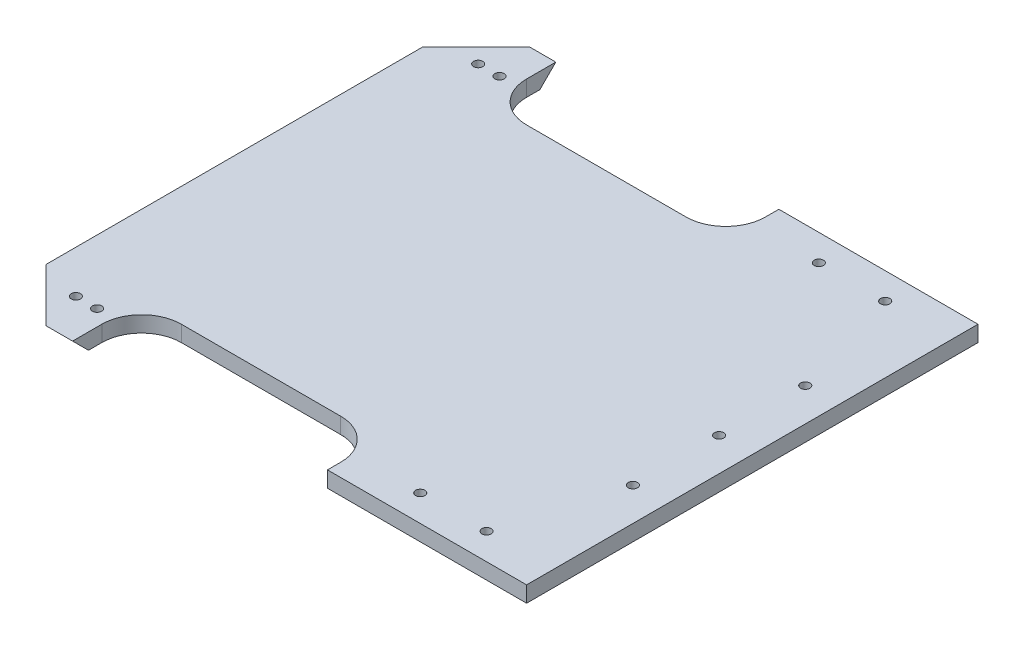
SolidWorks part; units mm, degrees
material "ABS"
ref_plane "Front Plane" through (0, 0, 0) normal (0, 0, 1) x (1, 0, 0)
ref_plane "Top Plane" through (0, 0, 0) normal (0, 1, 0) x (1, 0, 0)
ref_plane "Right Plane" through (0, 0, 0) normal (1, 0, 0) x (0, 0, -1)
sketch "Sketch1" plane through (0, 0, 0) normal (0, 1, 0) x (1, 0, 0)
  line L1 (-97.5, 85) -> (97.5, 85)
  line L2 (-97.5, 85) -> (-97.5, -85)
  line L3 (-97.5, -85) -> (97.5, -85)
  line L4 (97.5, 85) -> (97.5, -85)
  line L5 (-97.5, 85) -> (97.5, -85) construction
  line L6 (-97.5, -85) -> (97.5, 85) construction
  point P0 (0, 0)
  dimension "D1" = 195
  dimension "D2" = 170
extrude "Boss-Extrude1" add sketch "Sketch1" along normal blind 6
sketch "Sketch2" plane through (0, 6, 0) normal (0, 1, 0) x (1, 0, 0)
  line L0 (-97.5, -85) -> (-67.5, -85) construction
  line L1 (-97.5, -85) -> (97.5, -85) construction
  line L2 (0, 0) -> (-97.5, 0) construction
  line L3 (-67.5, -85) -> (22.5, -85)
  line L4 (-67.5, -85) -> (-67.5, -65)
  line L5 (-67.5, -65) -> (22.5, -65)
  line L6 (22.5, -85) -> (22.5, -65)
  line L7 (-97.5, 85) -> (-97.5, -85) construction
  line L8 (-67.5, 65) -> (22.5, 65)
  line L9 (22.5, 85) -> (22.5, 65)
  line L10 (-67.5, 85) -> (22.5, 85)
  line L11 (-67.5, 85) -> (-67.5, 65)
  dimension "D1" = 30
  dimension "D2" = 90
  dimension "D3" = 20
extrude "Cut-Extrude1" cut sketch "Sketch2" against normal through all
fillet "Fillet1" radius 15 4 edges at (22.5, 3, -65) (-67.5, 3, -65) (-67.5, 3, 65) (22.5, 3, 65)
sketch "Sketch3" plane through (0, 6, 0) normal (0, 1, 0) x (1, 0, 0)
  line L0 (0, 0) -> (-97.5, 0) construction
  line L1 (-67.5, 85) -> (-97.5, 85)
  line L2 (-67.5, 85) -> (-67.5, 91)
  line L3 (-67.5, 91) -> (-97.5, 91)
  line L4 (-97.5, 85) -> (-97.5, 91)
  line L5 (-97.5, 85) -> (-97.5, -85) construction
  line L6 (-67.5, -91) -> (-97.5, -91)
  line L7 (-97.5, -85) -> (-97.5, -91)
  line L8 (-67.5, -85) -> (-97.5, -85)
  line L9 (-67.5, -85) -> (-67.5, -91)
  dimension "D1" = 6
extrude "Boss-Extrude2" add sketch "Sketch3" against normal up to surface (6 mm away) up to face at (-16.875, 0, 0)
chamfer "Chamfer1" distance 20 angle 45 2 edges at (-97.5, 3, 91) (-97.5, 3, -91)
sketch "Sketch4" plane through (0, 6, 0) normal (0, 1, 0) x (1, 0, 0)
  line L0 (-67.5, 91) -> (-67.5, 80) construction
  line L1 (-67.5, 91.1) -> (-88.5, 91.1) construction
  line L2 (-67.5, 91.1) -> (-67.5, 68.1) construction
  line L3 (-67.5, 68.1) -> (-88.5, 68.1) construction
  line L4 (-88.5, 91.1) -> (-88.5, 68.1) construction
  line L5 (-81.5, 75.7667) -> (-73.5, 75.7667) construction
  line L7 (-88.5, 68.1) -> (-81.5, 75.7667) construction
  line L8 (-81.5, 75.7667) -> (-74.5, 83.4333) construction
  line L9 (-74.5, 83.4333) -> (-67.5, 91.1) construction
  line L10 (-97.5, 0) -> (0, 0) construction
  line L11 (-97.5, 71) -> (-97.5, -71) construction
  line L12 (-67.5, 91) -> (-77.5, 91) construction
  circle A0 centre (-81.5, 75.7667) radius 1.75
  circle A1 centre (-74.5, 83.4333) radius 1.75 construction
  circle A2 centre (-74.5, -83.4333) radius 1.75 construction
  circle A3 centre (-81.5, -75.7667) radius 1.75
  circle A4 centre (-73.5, 75.7667) radius 1.75
  circle A5 centre (-73.5, -75.7667) radius 1.75
  dimension "D4" = 3.5
  dimension "D5" = 3.5
  dimension "D6" = 3.5
  dimension "D1" = 23
  dimension "D2" = 21
  dimension "D3" = 0.1
  dimension "D7" = 8
extrude "Cut-Extrude2" cut sketch "Sketch4" against normal through all
sketch "Sketch7" plane through (0, 0, 0) normal (0, -1, 0) x (1, 0, 0)
  line L0 (97.5, 85) -> (97.5, -85) construction
  line L1 (22.5, 85.1) -> (97.5, 85.1) construction
  line L2 (22.5, 85.1) -> (22.5, 65) construction
  line L3 (22.5, 65) -> (97.5, 65) construction
  line L4 (97.5, 85.1) -> (97.5, 65) construction
  line L5 (22.5, 85) -> (22.5, 80) construction
  line L6 (22.5, 85) -> (97.5, 85) construction
  line L7 (22.5, 75.05) -> (47.5, 75.05) construction
  line L8 (47.5, 75.05) -> (72.5, 75.05) construction
  line L9 (72.5, 75.05) -> (97.5, 75.05) construction
  line L10 (0, 0) -> (97.5, 0) construction
  circle A0 centre (47.5, 75.05) radius 1.75
  circle A1 centre (72.5, 75.05) radius 1.75
  circle A2 centre (72.5, -75.05) radius 1.75
  circle A3 centre (47.5, -75.05) radius 1.75
  dimension "D3" = 3.5
  dimension "D4" = 3.5
  dimension "D1" = 0.1
  dimension "D2" = 20.1
extrude "Cut-Extrude5" cut sketch "Sketch7" against normal through all
sketch "Sketch8" plane through (0, 0, 0) normal (0, -1, 0) x (1, 0, 0)
  line L0 (97.5, 0) -> (72.5, 0) construction
  line L1 (97.5, 85) -> (97.5, -85) construction
  line L2 (85, 64.9) -> (85, 32.45) construction
  line L3 (72.5, 64.9) -> (97.5, 64.9) construction
  line L4 (72.5, 64.9) -> (72.5, -64.9) construction
  line L5 (72.5, -64.9) -> (97.5, -64.9) construction
  line L6 (97.5, 64.9) -> (97.5, -64.9) construction
  line L7 (72.5, 64.9) -> (97.5, -64.9) construction
  line L8 (72.5, -64.9) -> (97.5, 64.9) construction
  line L9 (85, 32.45) -> (85, 0) construction
  line L10 (85, 0) -> (85, -32.45) construction
  line L11 (85, -32.45) -> (85, -64.9) construction
  circle A0 centre (85, 32.45) radius 1.75
  circle A1 centre (85, 0) radius 1.75
  circle A2 centre (85, -32.45) radius 1.75
  point P5 (85, 0)
  dimension "D3" = 3.5
  dimension "D4" = 3.5
  dimension "D5" = 3.5
  dimension "D1" = 25
  dimension "D2" = 129.8
extrude "Cut-Extrude6" cut sketch "Sketch8" against normal through all
sketch "Sketch6" plane through (0, 0, 0) normal (0, -1, 0) x (1, 0, 0)
  line L0 (0, 0) -> (-97.5, 0) construction
  line L1 (-97.5, -71) -> (-97.5, 71) construction
  circle A0 centre (-73.5, 75.7667) radius 3.5
  circle A1 centre (-81.5, 75.7667) radius 3.5
  circle A2 centre (-73.5, -75.7667) radius 3.5
  circle A3 centre (-81.5, -75.7667) radius 3.5
  circle A4 centre (47.5, 75.05) radius 3.5
  circle A5 centre (72.5, 75.05) radius 3.5
  circle A6 centre (47.5, -75.05) radius 3.5
  circle A7 centre (72.5, -75.05) radius 3.5
  circle A8 centre (85, 32.45) radius 3.5
  circle A9 centre (85, 0) radius 3.5
  circle A10 centre (85, -32.45) radius 3.5
  point P34 (-74.5, 83.4333)
  point P35 (-74.5, 75.7667)
  dimension "D1" = 7
  dimension "D2" = 7
  dimension "D3" = 7
  dimension "D4" = 7
  dimension "D5" = 7
  dimension "D6" = 7
  dimension "D7" = 7
extrude "Cut-Extrude4" cut sketch "Sketch6" against normal blind 3
chamfer "Chamfer3" distance 6 angle 45 2 edges at (-72.5, 0, -91) (-72.5, 0, 91)
sketch "Sketch9" plane through (0, 6, 0) normal (0, 1, 0) x (1, 0, 0)
  line L0 (35.7816, 85) -> (35.7816, 48.8) construction
  line L1 (97.5, 85) -> (22.5, 85) construction
  line L2 (35.7816, 48.8) -> (35.7816, -48.8) construction
  line L3 (35.7816, -48.8) -> (35.7816, -85) construction
  line L4 (22.5, -85) -> (97.5, -85) construction
  circle A0 centre (35.7816, 48.8) radius 2.35
  circle A1 centre (35.7816, -48.8) radius 2.35
  dimension "D2" = 4.7
  dimension "D3" = 4.7
  dimension "D1" = 97.6
